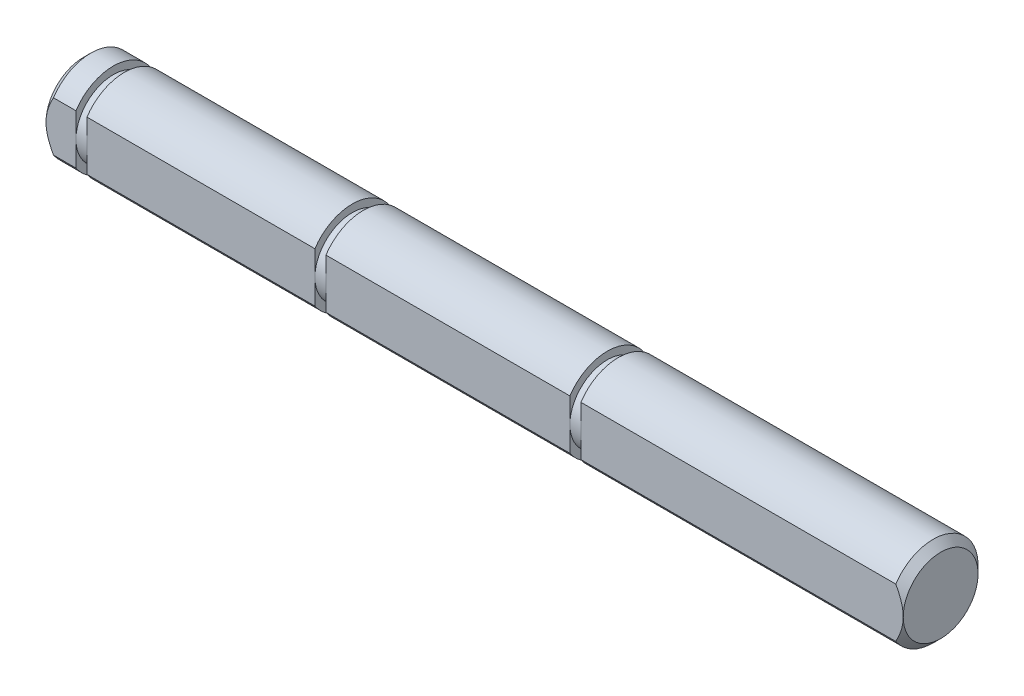
SolidWorks part; units mm, degrees
material "AISI 1020 Steel, Cold Rolled"
ref_plane "Front" through (0, 0, 0) normal (0, 0, 1) x (1, 0, 0)
ref_plane "Top" through (0, 0, 0) normal (0, 1, 0) x (1, 0, 0)
ref_plane "Right" through (0, 0, 0) normal (1, 0, 0) x (0, 0, -1)
ref_axis "side-side" through (80.9, 0, 0) along (-1, 0, 0)
ref_axis "up-down" through (0, 50, 0) along (0, -1, 0)
ref_axis "front-back" through (0, 0, -80.9) along (0, 0, 1)
sketch "Sketch1" plane through (0, 0, 0) normal (0, 0, 1) x (1, 0, 0)
  line L0 (-17.9666, 0) -> (-31.2893, 0) construction
  line L1 (-17.9666, 0) -> (39.3098, 0)
  line L2 (-17.9666, 0) -> (-17.9666, 3)
  line L3 (-17.9666, 3) -> (-15.9666, 3)
  line L4 (39.3098, 0) -> (39.3098, 3)
  line L6 (0, 3) -> (0, 2.5)
  line L7 (0, 2.5) -> (0.7366, 2.5)
  line L8 (0.7366, 3) -> (0.7366, 2.5)
  line L10 (-15.9666, 3) -> (-15.9666, 2.5)
  line L11 (-15.9666, 2.5) -> (-15.23, 2.5)
  line L12 (-15.23, 3) -> (-15.23, 2.5)
  line L14 (17.0366, 3) -> (17.0366, 2.5)
  line L15 (17.0366, 2.5) -> (17.7732, 2.5)
  line L16 (17.7732, 3) -> (17.7732, 2.5)
  line L18 (36.5732, 3) -> (36.5732, 2.5) construction
  line L19 (36.5732, 2.5) -> (37.3098, 2.5) construction
  line L20 (37.3098, 3) -> (37.3098, 2.5) construction
  line L21 (37.3098, 3) -> (39.3098, 3)
  line L22 (17.7732, 3) -> (36.5732, 3)
  line L23 (0.7366, 3) -> (17.0366, 3)
  line L24 (-15.23, 3) -> (0, 3)
  line L25 (36.5732, 3) -> (37.3098, 3)
  dimension "D1" = 6
  dimension "D2" = 0.7366
  dimension "D3" = 15.23
  dimension "D4" = 2
  dimension "D5" = 5
  dimension "D6" = 16.3
  dimension "D7" = 18.8
  dimension "D8" = 2
revolve "Revolve1" add sketch "Sketch1" angle 360 about L0
chamfer "Chamfer1" distance 0.5 angle 45 2 edges at (39.3098, 0, -3) (-17.9666, 0, -3)
sketch "Sketch2" plane through (0, 0, 0) normal (1, 0, 0) x (0, 0, -1)
  line L1 (-4.5, 3) -> (-2.5, 3)
  line L2 (-4.5, 3) -> (-4.5, -3)
  line L3 (-4.5, -3) -> (-2.5, -3)
  line L4 (-2.5, 3) -> (-2.5, -3)
  point P5 (-2.5, 0)
  dimension "D1" = 2.5
  dimension "D2" = 6
  dimension "D3" = 2
extrude "Cut-Extrude1" cut sketch "Sketch2" against normal through all both and the other way through all
